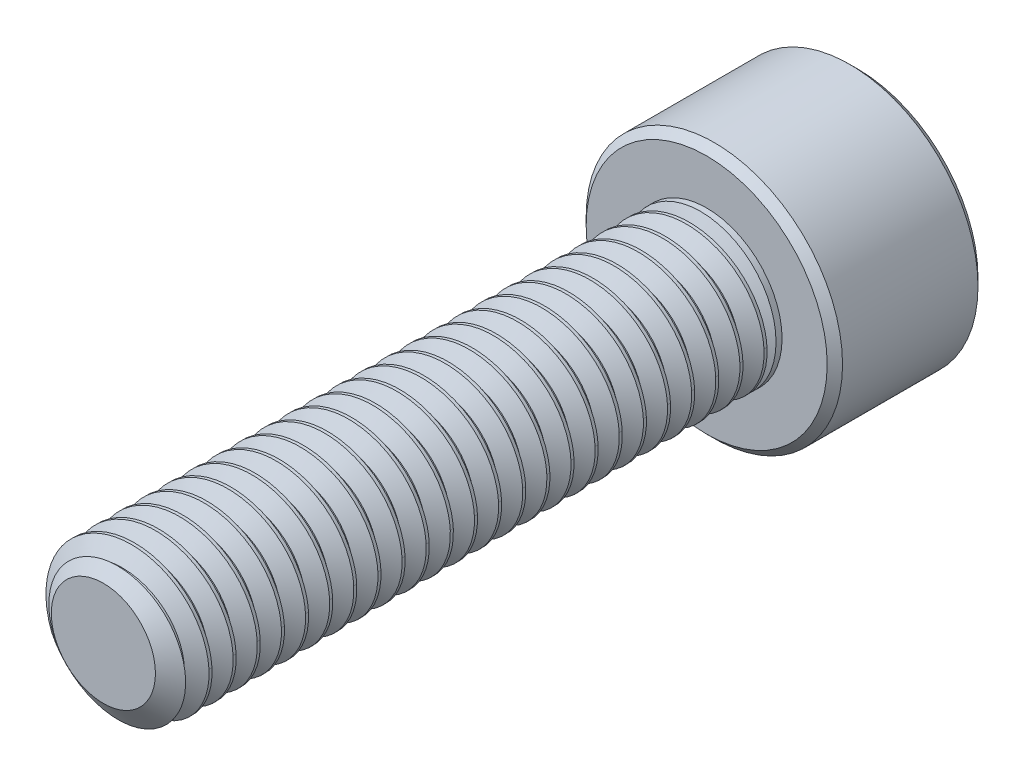
SolidWorks part; units mm, degrees
ref_plane "Front Plane" through (0, 0, 0) normal (0, 0, 1) x (1, 0, 0)
ref_plane "Top Plane" through (0, 0, 0) normal (0, 1, 0) x (1, 0, 0)
ref_plane "Right Plane" through (0, 0, 0) normal (1, 0, 0) x (0, 0, -1)
sketch "Sketch1" plane through (0, 0, 0) normal (0, 0, 1) x (1, 0, 0)
  circle A0 centre (0, 0) radius 2.5
  dimension "OD" = 5
extrude "Extrude1" add sketch "Sketch1" against normal blind 20
sketch "Sketch2" plane through (0, 0, 0) normal (0, 0, 1) x (1, 0, 0)
  circle A0 centre (0, 0) radius 2.5 construction
  circle A1 centre (0, 0) radius 2.5
curve "Helix/Spiral1" pitch 0.8 height 20.8 turns 26 parameters "pitch"=0.8
sketch "Sketch3" plane through (0, 0, 0) normal (1, 0, 0) x (0, 0, -1)
  line L0 (-0.7, 2.5) -> (-0.4, 1.9804)
  line L1 (-0.4, 1.9804) -> (-0.3, 1.9804)
  line L2 (-0.3, 1.9804) -> (0, 2.5)
  line L3 (-0.7, 2.5) -> (0, 2.5)
  line L4 (-0.35, 2.5) -> (-0.35, 1.9804) construction
  line L5 (-0.55, 2.2402) -> (-0.15, 2.2402) construction
  line L6 (0, 2.5) -> (0, -2.5) construction
  line L7 (0, -2.5) -> (20, -2.5) construction
  point P11 (3.6, -2.5)
  dimension "D1" = 0.1
  dimension "D2" = 0.4
  dimension "D3" = 60
  dimension "D4" = 3.6
sweep "Cut-Sweep1" cut profiles "Sketch3" path "Helix/Spiral1"
sketch "Sketch4" plane through (0, 0, 0) normal (1, 0, 0) x (0, 0, -1)
  line L0 (0.5417, 2.5) -> (0, 1.7264)
  line L1 (0, 1.7264) -> (0, 2.5)
  line L2 (0.5417, 2.5) -> (0, 2.5)
  line L3 (-0.7, 2.5) -> (0, 2.5) construction
  line L4 (0, 0) -> (7.0209, 0) construction
  dimension "D1" = 55
  dimension "D2" = 0.254
revolve "Cut-Revolve1" cut sketch "Sketch4" angle 360 about L4
sketch "Sketch5" plane through (0, 0, 0) normal (1, 0, 0) x (0, 0, -1)
  line L0 (20, -1.991) -> (20, 1.7838) construction
  line L1 (20, 2.5) -> (0.1203, 2.5)
  line L2 (20, 2.5) -> (20, 0)
  line L3 (20, 0) -> (0.0001, 0)
  line L4 (0.0001, 2.1698) -> (0.0001, 0)
  line L5 (0.1203, 2.5) -> (0.0001, 2.1698)
  line L6 (0, 0) -> (9.9695, 0) construction
  point P3 (0.0001, 2.5)
  point P10 (0.0001, 2.5)
  dimension "D1" = 0.3302
  dimension "Thread min" = 0.0001
  dimension "D3" = 20
revolve "partially thread" [suppressed] add sketch "Sketch5" angle 360 about L6
sketch "Sketch6" plane through (0, 0, -20) normal (0, 0, -1) x (-1, 0, 0)
  circle A0 centre (0, 0) radius 4.25
  dimension "head dia" = 8.5
extrude "Extrude2" add sketch "Sketch6" along normal blind 5
sketch "Sketch7" plane through (0, 0, -25) normal (0, 0, -1) x (-1, 0, 0)
  line L1 (0, 2.3094) -> (-2, 1.1547)
  line L2 (-2, 1.1547) -> (-2, -1.1547)
  line L3 (-2, -1.1547) -> (0, -2.3094)
  line L4 (0, -2.3094) -> (2, -1.1547)
  line L5 (2, -1.1547) -> (2, 1.1547)
  line L6 (2, 1.1547) -> (0, 2.3094)
  circle A0 centre (0, 0) radius 2 construction
  dimension "hex dia" = 4
extrude "Cut-Extrude1" cut sketch "Sketch7" against normal blind 3
sketch "Sketch8" plane through (0, 0, -25) normal (0, 0, -1) x (-1, 0, 0)
  circle A0 centre (0, 0) radius 2.3094
extrude "Cut-Extrude2" cut sketch "Sketch8" against normal through all draft 45
chamfer "Chamfer1" distance 0.255 angle 45 2 edges at (-4.25, 0, -25) (-4.25, 0, -20)
sketch "Sketch9" plane through (0, 0, 0) normal (1, 0, 0) x (0, 0, -1)
  line L0 (0, 2.5) -> (0, -2.5) construction
  line L1 (4.4, 2.5) -> (4.4, -2.5) construction
  dimension "D1" = 4.4
sketch "Sketch10" plane through (0, 0, 0) normal (1, 0, 0) x (0, 0, -1)
  line L0 (20, 2.5) -> (20, 0)
  line L1 (20, 2.5) -> (19.8, 2.5)
  line L2 (19.8, 2.5) -> (18.7645, 0)
  line L3 (20, 0) -> (18.7645, 0)
  line L4 (20, 3.995) -> (20, -3.995) construction
  dimension "D1" = 22.5
  dimension "D2" = 0.2
revolve "Revolve1" add sketch "Sketch10" angle 360 about L3
equation "\"D3@Helix/Spiral1\" = \"screw length@Extrude1\"+\"pitch@Helix/Spiral1\""
equation "\"D1@Sketch3\" = \"pitch@Helix/Spiral1\"*.125"
equation "\"D2@Sketch3\" = \"pitch@Helix/Spiral1\"*.5"
equation "\"D1@Cut-Extrude1\" = \"hex dia@Sketch7\"*.75"
equation "\"D1@Chamfer1\" = \"head dia@Sketch6\"*.03"
equation "\"D1@Sketch9\" = \"pitch@Helix/Spiral1\"*5.5"
equation "\"D2@Sketch10\" = \"pitch@Helix/Spiral1\"*.25"
equation "\"D4@Sketch3\" = \"pitch@Helix/Spiral1\"*4.50"
